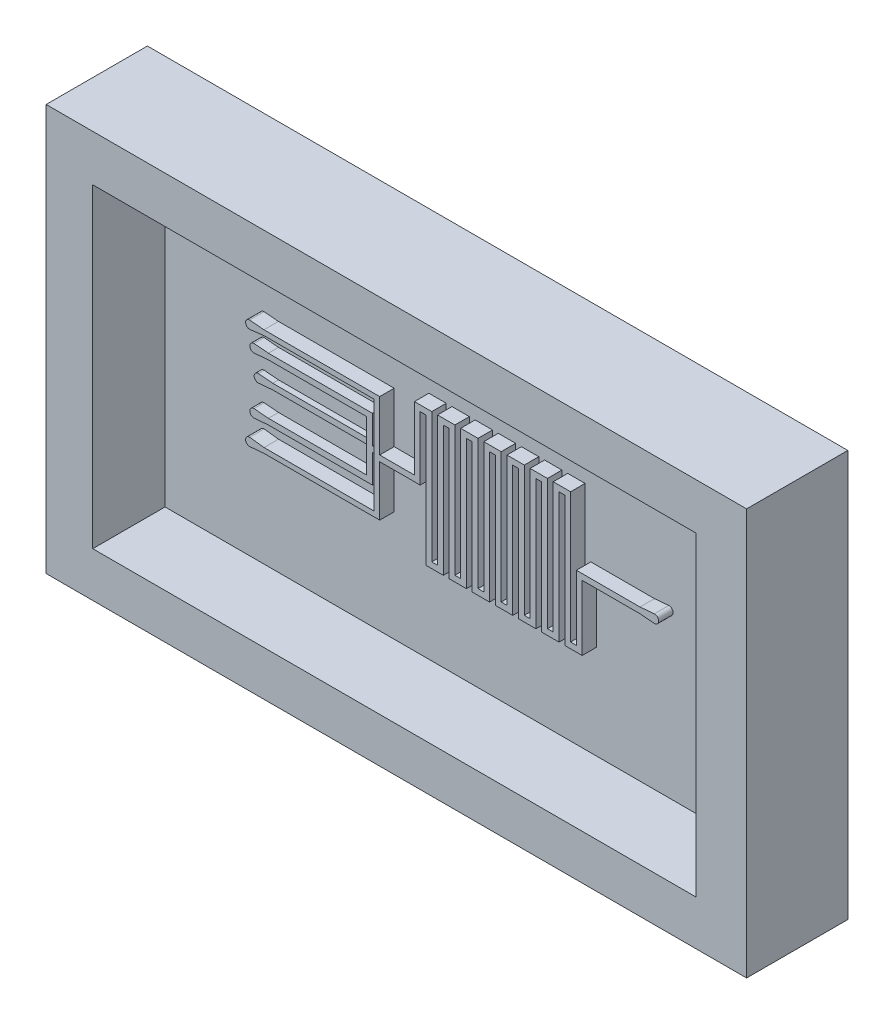
SolidWorks part; units mm, degrees
note: The reader was unsure of these and kept them because the rebuilt part matched: shared geometry of "Sketch1<4>", "Sketch1<5>".
ref_plane "Front Plane" through (0, 0, 0) normal (0, 0, 1) x (1, 0, 0)
ref_plane "Top Plane" through (0, 0, 0) normal (0, 1, 0) x (1, 0, 0)
ref_plane "Right Plane" through (0, 0, 0) normal (1, 0, 0) x (0, 0, -1)
sketch "Sketch1" plane through (0, 0, 0) normal (0, 0, 1) x (1, 0, 0)
  line L0 (0.6, 0.0927) -> (1.8, 0.0927)
  line L5 (0.6, 1.8427) -> (0.6, 0.0927)
  line L8 (0.4029, 1.6672) -> (0.4029, 0.0927)
  line L18 (0.4029, 0.0927) -> (0.2029, 0.0927)
  line L20 (-3.3971, 1.0672) -> (0.2029, 1.0672)
  line L22 (0.6, 1.8427) -> (-3.4, 1.8427)
  line L23 (0.4029, 1.6672) -> (-3.3971, 1.6672)
  line L24 (0.2029, 1.0672) -> (0.2029, 0.0927)
  line L26 (2, -0.1073) -> (0.6, -0.1073)
  line L27 (0.4029, 0.0927) -> (0.4029, -0.1073)
  line L30 (1.8, 0.0927) -> (1.8, 2.2927)
  line L31 (2, -0.1073) -> (2, 2.0906)
  line L32 (2, 2.0906) -> (2.2, 2.0906)
  line L33 (1.8, 2.2927) -> (2.4, 2.2927)
  line L34 (2.2, 2.0906) -> (2.2, -2.4094)
  line L35 (2.4, 2.2927) -> (2.4, -2.2073)
  line L36 (2.4, -2.2073) -> (2.6, -2.2073)
  line L37 (2.2, -2.4094) -> (2.8, -2.4094)
  line L38 (2.6, -2.2073) -> (2.6, 2.2927)
  line L39 (2.8, -2.4094) -> (2.8, 2.0906)
  line L40 (2.6, 2.2927) -> (3.2, 2.2927)
  line L41 (2.8, 2.0906) -> (3, 2.0906)
  line L42 (3, 2.0906) -> (3, -2.4094)
  line L43 (3.2, 2.2927) -> (3.2, -2.2073)
  line L44 (3.2, -2.2073) -> (3.4, -2.2073)
  line L45 (3, -2.4094) -> (3.6, -2.4094)
  line L46 (3.4, -2.2073) -> (3.4, 2.2927)
  line L47 (3.6, -2.4094) -> (3.6, 2.0906)
  line L48 (3.4, 2.2927) -> (4, 2.2927)
  line L49 (3.6, 2.0906) -> (3.8, 2.0906)
  line L50 (3.8, 2.0906) -> (3.8, -2.4094)
  line L51 (4, 2.2927) -> (4, -2.2073)
  line L52 (4, -2.2073) -> (4.2, -2.2073)
  line L53 (3.8, -2.4094) -> (4.4, -2.4094)
  line L54 (4.2, -2.2073) -> (4.2, 2.2927)
  line L55 (4.4, -2.4094) -> (4.4, 2.0906)
  line L56 (4.2, 2.2927) -> (4.8, 2.2927)
  line L57 (4.4, 2.0906) -> (4.6, 2.0906)
  line L58 (4.6, 2.0906) -> (4.6, -2.4094)
  line L59 (4.8, 2.2927) -> (4.8, -2.2073)
  line L60 (4.8, -2.2073) -> (5, -2.2073)
  line L61 (4.6, -2.4094) -> (5.2, -2.4094)
  line L62 (5, -2.2073) -> (5, 2.2927)
  line L63 (5.2, -2.4094) -> (5.2, 2.0906)
  line L64 (5, 2.2927) -> (5.6, 2.2927)
  line L65 (5.2, 2.0906) -> (5.4, 2.0906)
  line L66 (5.4, 2.0906) -> (5.4, -2.4094)
  line L67 (5.6, 2.2927) -> (5.6, -2.2073)
  line L68 (5.6, -2.2073) -> (5.8, -2.2073)
  line L69 (5.4, -2.4094) -> (6, -2.4094)
  line L70 (5.8, -2.2073) -> (5.8, 2.2927)
  line L71 (6, -2.4094) -> (6, 2.0906)
  line L72 (5.8, 2.2927) -> (6.4, 2.2927)
  line L73 (6, 2.0906) -> (6.2, 2.0906)
  line L74 (6.2, 2.0906) -> (6.2, -2.4094)
  line L75 (6.4, 2.2927) -> (6.4, -2.2073)
  line L76 (6.4, -2.2073) -> (6.6, -2.2073)
  line L77 (6.2, -2.4094) -> (6.8, -2.4094)
  line L78 (6.6, -2.2073) -> (6.6, 2.2927)
  line L79 (6.8, -2.4094) -> (6.8, 2.0906)
  line L80 (6.6, 2.2927) -> (7.2, 2.2927)
  line L81 (6.8, 2.0906) -> (7, 2.0906)
  line L82 (7, 2.0906) -> (7, -2.4094)
  line L83 (7.2, 2.2927) -> (7.2, -2.2073)
  line L84 (7.2, -2.2073) -> (7.4, -2.2073)
  line L85 (7, -2.4094) -> (7.6, -2.4094)
  line L86 (9.6, 0.0427) -> (10.0981, 0.0863)
  line L87 (9.6, -0.1594) -> (10.0981, -0.203)
  line L88 (7.4, 0.0427) -> (9.6, 0.0427)
  line L89 (7.6, -0.1594) -> (9.6, -0.1594)
  line L90 (7.4, -2.2073) -> (7.4, 0.0427)
  line L91 (7.6, -2.4094) -> (7.6, -0.1594)
  line L93 (7.6, -2.4094) -> (7.6, 2.0906) [skipped]
  line L94 (7.4, -2.2073) -> (7.4, 2.2927) [skipped]
  line L99 (-3.3971, 0.0927) -> (0.0029, 0.0927)
  line L100 (-3.3971, 0.8672) -> (0.0029, 0.8672)
  line L101 (0.0029, 0.8672) -> (0.0029, 0.0927)
  line L105 (-3.4, -1.8573) -> (-3.8981, -1.9009)
  line L106 (-3.3971, 0.0927) -> (-3.8952, 0.1363)
  line L107 (-3.3971, -0.1073) -> (0.0029, -0.1073)
  line L108 (0.0029, 0.0927) -> (0.0029, -0.1073)
  line L109 (-3.3971, 1.0672) -> (-3.8952, 1.1108)
  line L110 (-3.3971, 0.8672) -> (-3.8952, 0.8236)
  line L111 (-3.4, 1.8427) -> (-3.8981, 1.8863)
  line L112 (-3.3971, 1.6672) -> (-3.8935, 1.6076)
  line L113 (-3.3971, -1.6818) -> (-3.8935, -1.6222)
  line L114 (-3.3971, -0.8818) -> (-3.8952, -0.8382)
  line L115 (-3.3971, -1.0818) -> (-3.8952, -1.1253)
  line L116 (-3.3971, -1.0818) -> (0.2029, -1.0818)
  line L117 (-3.3971, -0.8818) -> (0.0029, -0.8818)
  line L118 (0.0029, -0.8818) -> (0.0029, -0.1073)
  line L119 (0.2029, -1.0818) -> (0.2029, -0.1073)
  line L120 (0.4029, -0.1073) -> (0.2029, -0.1073)
  line L121 (-3.3971, -0.1073) -> (-3.8952, -0.1509)
  line L122 (0.6, -1.8573) -> (0.6, -0.1073)
  line L123 (0.4029, -1.6818) -> (0.4029, -0.1073)
  line L124 (0.4029, -1.6818) -> (-3.3971, -1.6818)
  line L125 (0.6, -1.8573) -> (-3.4, -1.8573)
  arc A0 (-3.8981, 1.8863) -> (-3.8935, 1.6076) centre (-3.8958, 1.747) ccw
  arc A1 (-3.8952, 1.1108) -> (-3.8952, 0.8236) centre (-3.8952, 0.9672) ccw
  arc A2 (10.0981, 0.0863) -> (10.0981, -0.203) centre (10.0981, -0.0583) cw
  arc A3 (-3.8981, -1.9009) -> (-3.8935, -1.6222) centre (-3.8958, -1.7615) cw
  arc A4 (-3.8952, -1.1253) -> (-3.8952, -0.8382) centre (-3.8952, -0.9818) cw
  arc A5 (-3.8952, 0.1363) -> (-3.8952, -0.1509) centre (-3.8952, -0.0073) ccw
  dimension "D31" = 0.5
  dimension "D5" = 0.2
  dimension "D6" = 4
  dimension "D9" = 2.2
  dimension "D10" = 0.2
  dimension "D11" = 0.6
  dimension "D12" = 4.5
  dimension "D13" = 4.5
  dimension "D14" = 0.2
  dimension "D15" = 0.6
  dimension "D16" = 4.5
  dimension "D17" = 7
  dimension "D18" = 2.2
  dimension "D19" = 2
  dimension "D20" = 0.5
  dimension "D21" = 175
  dimension "D22" = 0.5
  dimension "D23" = 175
  dimension "D32" = 0.5
  dimension "D34" = 0.5
  dimension "D36" = 0.5
  dimension "D37" = 0.5
  dimension "D38" = 175
  dimension "D39" = 173.157
  dimension "D41" = 0.5
extrude "Boss-Extrude1" add sketch "Sketch1" along normal blind 0.2
extrude "Boss-Extrude2" add sketch "Sketch1<4>" along normal blind 0.35
sketch "Sketch1<4>" plane through (0, 0, 0) normal (0, 0, 1) x (1, 0, 0) same geometry as "Sketch1"
extrude "Boss-Extrude3" add sketch "Sketch1<5>" along normal blind 0.5
sketch "Sketch1<5>" plane through (0, 0, 0) normal (0, 0, 1) x (1, 0, 0) same geometry as "Sketch1"
sketch "Sketch2" plane through (0, 0, 0) normal (0, 0, -1) x (-1, 0, 0)
  line L1 (7.3195, -5.672) -> (-13.5394, -5.672)
  line L2 (7.3195, -5.672) -> (7.3195, 5.2238)
  line L3 (7.3195, 5.2238) -> (-13.5394, 5.2238)
  line L4 (-13.5394, -5.672) -> (-13.5394, 5.2238)
extrude "Boss-Extrude4" add sketch "Sketch2" along normal blind 1
sketch "Sketch3" plane through (0, 0, -1) normal (0, 0, -1) x (-1, 0, 0)
  line L1 (7.3195, -5.672) -> (-13.5394, -5.672)
  line L2 (7.3195, -5.672) -> (7.3195, 5.2238)
  line L3 (7.3195, 5.2238) -> (-13.5394, 5.2238)
  line L4 (-13.5394, -5.672) -> (-13.5394, 5.2238)
  line L5 (8.9303, -7.2222) -> (-15.2846, -7.2222)
  line L6 (8.9303, -7.2222) -> (8.9303, 6.8229)
  line L7 (8.9303, 6.8229) -> (-15.2846, 6.8229)
  line L8 (-15.2846, -7.2222) -> (-15.2846, 6.8229)
extrude "Boss-Extrude5" add sketch "Sketch3" against normal blind 3.5
